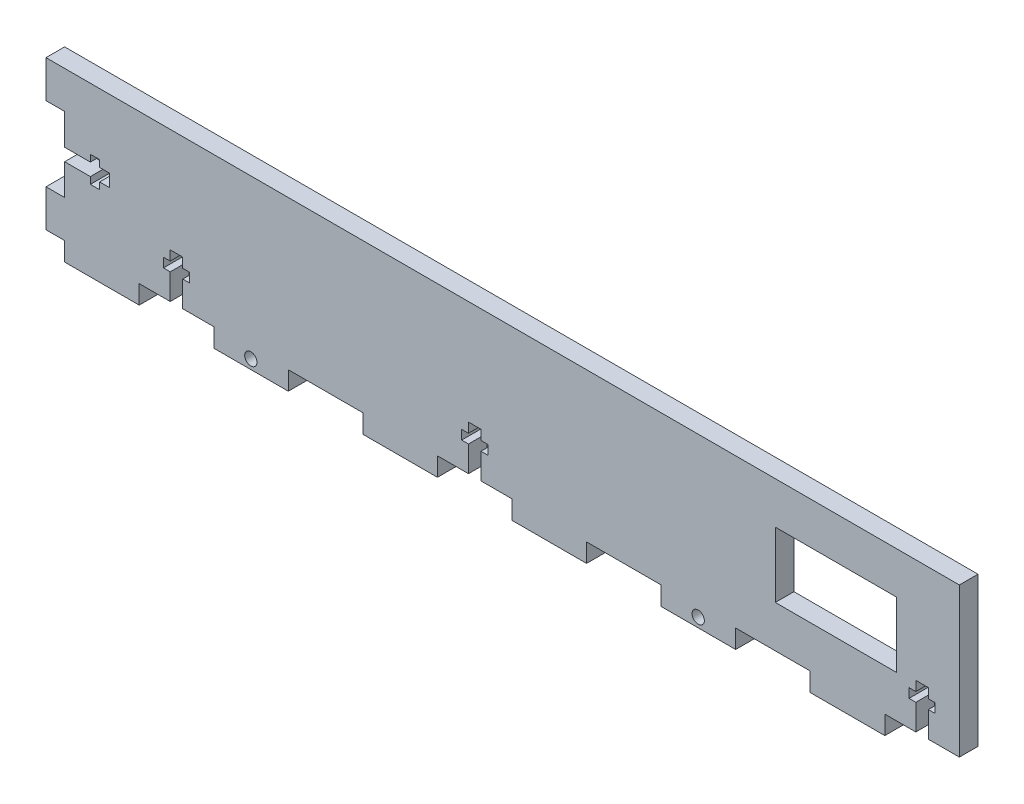
SolidWorks part; units mm, degrees
ref_plane "Front Plane" through (0, 0, 0) normal (0, 0, 1) x (1, 0, 0)
ref_plane "Top Plane" through (0, 0, 0) normal (0, 1, 0) x (1, 0, 0)
ref_plane "Right Plane" through (0, 0, 0) normal (1, 0, 0) x (0, 0, -1)
sketch "Sketch1" plane through (0, 0, 0) normal (0, 0, 1) x (1, 0, 0)
  line L0 (-262.733, -54.9538) -> (-262.733, 69.85) construction
  line L1 (42.067, 25.4) -> (-262.733, 25.4)
  line L2 (42.067, 25.4) -> (42.067, -25.4)
  line L3 (42.067, -25.4) -> (-262.733, -25.4)
  line L4 (-262.733, 25.4) -> (-262.733, -25.4)
  line L5 (63.0291, 0) -> (-62.7737, 0) construction
  line L6 (-19.6295, 10.033) -> (19.6295, 10.033) construction
  line L7 (19.6295, -10.033) -> (-19.6295, -10.033) construction
  line L8 (27.25, 6.27) -> (27.25, 8.0899) construction
  dimension "D1" = 50.8
  dimension "D2" = 14.817
extrude "Boss-Extrude1" add sketch "Sketch1" along normal blind 6.35
sketch "Sketch2" plane through (0, 0, 6.35) normal (0, 0, 1) x (1, 0, 0)
  line L0 (-41.9443, 0) -> (30.2812, 0) construction
  line L1 (-20.6375, 11.1125) -> (20.6375, 11.1125)
  line L2 (-20.6375, 11.1125) -> (-20.6375, -11.1125)
  line L3 (-20.6375, -11.1125) -> (20.6375, -11.1125)
  line L4 (20.6375, 11.1125) -> (20.6375, -11.1125)
  line L5 (-19.6295, 10.033) -> (19.6295, 10.033) construction
  line L6 (19.6295, -10.033) -> (-19.6295, -10.033) construction
  line L7 (0, 34.6052) -> (0, -28.4279) construction
  line L8 (-20.1295, -9.533) -> (-20.1295, 9.533) construction
  line L9 (20.1295, 9.533) -> (20.1295, -9.533) construction
  dimension "D1" = 22.225
  dimension "D2" = 41.275
extrude "Cut-Extrude1" cut sketch "Sketch2" against normal through all
ref_plane "Plane1" through (42.067, -25.4, 6.35) normal (1, 0, 0) x (0, 0, -1)
sketch "Sketch5" plane through (0, -25.4, 0) normal (0, -1, 0) x (1, 0, 0)
  line L0 (-262.733, 6.35) -> (42.067, 6.35) construction
  line L1 (16.667, 6.35) -> (-8.733, 6.35)
  line L2 (16.667, 6.35) -> (16.667, 0)
  line L3 (16.667, 0) -> (-8.733, 0)
  line L4 (-8.733, 6.35) -> (-8.733, 0)
  line L5 (-262.733, 0) -> (42.067, 0) construction
  dimension "D1" = 25.4
  dimension "D2" = 25.4
extrude "Boss-Extrude2" add sketch "Sketch5" along normal blind 6.35
pattern_linear "LPattern1" count 6 spacing 50.8 along (-1, 0, 0) of "Boss-Extrude2"
sketch "Sketch6" plane through (-262.733, 0, 0) normal (-1, 0, 0) x (0, 0, 1)
  line L0 (0, 25.4) -> (6.35, 25.4)
  line L1 (6.35, 25.4) -> (6.35, 12.7)
  line L2 (6.35, 25.4) -> (6.35, -31.75) construction
  line L3 (6.35, 12.7) -> (0, 12.7)
  line L4 (0, 25.4) -> (0, -31.75) construction
  line L5 (0, 12.7) -> (0, 25.4)
  dimension "D1" = 12.7
extrude "Boss-Extrude3" add sketch "Sketch6" along normal blind 6.35
pattern_linear "LPattern2" count 2 spacing 38.1 along (0, -1, 0) of "Boss-Extrude3"
sketch "Sketch7" plane through (0, 0, 6.35) normal (0, 0, 1) x (1, 0, 0)
  line L0 (-257.1687, 0) -> (-223.3079, 0) construction
  line L1 (-269.083, 12.7) -> (-262.733, 12.7) construction
  line L2 (-269.083, -12.7) -> (-262.733, -12.7) construction
  line L3 (-262.733, 12.7) -> (-262.733, -12.7) construction
  line B0 (-262.733, 2.1336) -> (-262.733, -2.1336)
  line B1 (-250.795, -2.1336) -> (-250.795, -4.445)
  line B2 (-250.795, -4.445) -> (-253.97, -4.445)
  line B3 (-253.97, -4.445) -> (-253.97, -2.1336)
  line B4 (-253.97, -2.1336) -> (-262.733, -2.1336)
  line B5 (-250.795, -2.1336) -> (-247.493, -2.1336)
  line B6 (-247.493, -2.1336) -> (-247.493, 2.1336)
  line B7 (-250.795, 2.1336) -> (-247.493, 2.1336)
  line B8 (-253.97, 2.1336) -> (-262.733, 2.1336)
  line B9 (-253.97, 4.445) -> (-253.97, 2.1336)
  line B10 (-250.795, 4.445) -> (-253.97, 4.445)
  line B11 (-250.795, 2.1336) -> (-250.795, 4.445)
sketch_block_instance "TSlot-1"
sketch_block "TSlot" parameters "D1"=3.302, "D2"=3.175
extrude "Cut-Extrude2" cut sketch "Sketch7" against normal through all
sketch "Sketch8" plane through (0, 0, 6.35) normal (0, 0, 1) x (1, 0, 0)
  line L0 (29.367, -1.7985) -> (29.367, -25.4) construction
  line L1 (16.667, -25.4) -> (42.067, -25.4) construction
  line L2 (42.067, -25.4) -> (42.067, 25.4) construction
  line L3 (16.667, -31.75) -> (16.667, -25.4) construction
  line L4 (-224.633, 2.3642) -> (-224.633, -25.4) construction
  line L5 (-237.333, -25.4) -> (-211.933, -25.4) construction
  line L6 (-237.333, -31.75) -> (-237.333, -25.4) construction
  line L7 (-211.933, -31.75) -> (-211.933, -25.4) construction
  line L8 (-123.033, 2.3642) -> (-123.033, -25.4) construction
  line L9 (-135.733, -25.4) -> (-110.333, -25.4) construction
  line L10 (-135.733, -31.75) -> (-135.733, -25.4) construction
  line L11 (-110.333, -31.75) -> (-110.333, -25.4) construction
  line B0 (-226.7666, -25.4) -> (-222.4994, -25.4)
  line B1 (-222.4994, -13.462) -> (-220.188, -13.462)
  line B2 (-220.188, -13.462) -> (-220.188, -16.637)
  line B3 (-220.188, -16.637) -> (-222.4994, -16.637)
  line B4 (-222.4994, -16.637) -> (-222.4994, -25.4)
  line B5 (-222.4994, -13.462) -> (-222.4994, -10.16)
  line B6 (-222.4994, -10.16) -> (-226.7666, -10.16)
  line B7 (-226.7666, -13.462) -> (-226.7666, -10.16)
  line B8 (-226.7666, -16.637) -> (-226.7666, -25.4)
  line B9 (-229.078, -16.637) -> (-226.7666, -16.637)
  line B10 (-229.078, -13.462) -> (-229.078, -16.637)
  line B11 (-226.7666, -13.462) -> (-229.078, -13.462)
  line B12 (-125.1666, -25.4) -> (-120.8994, -25.4)
  line B13 (-120.8994, -13.462) -> (-118.588, -13.462)
  line B14 (-118.588, -13.462) -> (-118.588, -16.637)
  line B15 (-118.588, -16.637) -> (-120.8994, -16.637)
  line B16 (-120.8994, -16.637) -> (-120.8994, -25.4)
  line B17 (-120.8994, -13.462) -> (-120.8994, -10.16)
  line B18 (-120.8994, -10.16) -> (-125.1666, -10.16)
  line B19 (-125.1666, -13.462) -> (-125.1666, -10.16)
  line B20 (-125.1666, -16.637) -> (-125.1666, -25.4)
  line B21 (-127.478, -16.637) -> (-125.1666, -16.637)
  line B22 (-127.478, -13.462) -> (-127.478, -16.637)
  line B23 (-125.1666, -13.462) -> (-127.478, -13.462)
  line B24 (27.2334, -25.4) -> (31.5006, -25.4)
  line B25 (31.5006, -13.462) -> (33.812, -13.462)
  line B26 (33.812, -13.462) -> (33.812, -16.637)
  line B27 (33.812, -16.637) -> (31.5006, -16.637)
  line B28 (31.5006, -16.637) -> (31.5006, -25.4)
  line B29 (31.5006, -13.462) -> (31.5006, -10.16)
  line B30 (31.5006, -10.16) -> (27.2334, -10.16)
  line B31 (27.2334, -13.462) -> (27.2334, -10.16)
  line B32 (27.2334, -16.637) -> (27.2334, -25.4)
  line B33 (24.922, -16.637) -> (27.2334, -16.637)
  line B34 (24.922, -13.462) -> (24.922, -16.637)
  line B35 (27.2334, -13.462) -> (24.922, -13.462)
sketch_block_instance "TSlot-2"
sketch_block_instance "TSlot-4"
sketch_block_instance "TSlot-5"
extrude "Cut-Extrude3" cut sketch "Sketch8" against normal through all
sketch "Sketch9" plane through (0, 0, 0) normal (0, 0, -1) x (-1, 0, 0)
  line L0 (44.7707, -31.75) -> (49.0379, -25.4) construction
  line L1 (59.533, -31.75) -> (34.133, -31.75) construction
  line L2 (44.7707, -31.75) -> (44.7707, -25.4) construction
  line L3 (49.0379, -31.75) -> (44.7707, -25.4) construction
  line L4 (49.0379, -25.4) -> (49.0379, -31.75) construction
  line L5 (197.1707, -31.75) -> (201.4379, -25.4) construction
  line L6 (197.1707, -31.75) -> (197.1707, -25.4) construction
  line L7 (211.933, -31.75) -> (186.533, -31.75) construction
  line L8 (201.4379, -31.75) -> (197.1707, -25.4) construction
  line L9 (201.4379, -25.4) -> (201.4379, -31.75) construction
  circle A0 centre (46.9043, -28.575) radius 2.0955
  circle A1 centre (199.3043, -28.575) radius 2.0955
  dimension "D1" = 4.191
extrude "Cut-Extrude4" cut sketch "Sketch9" against normal through all
